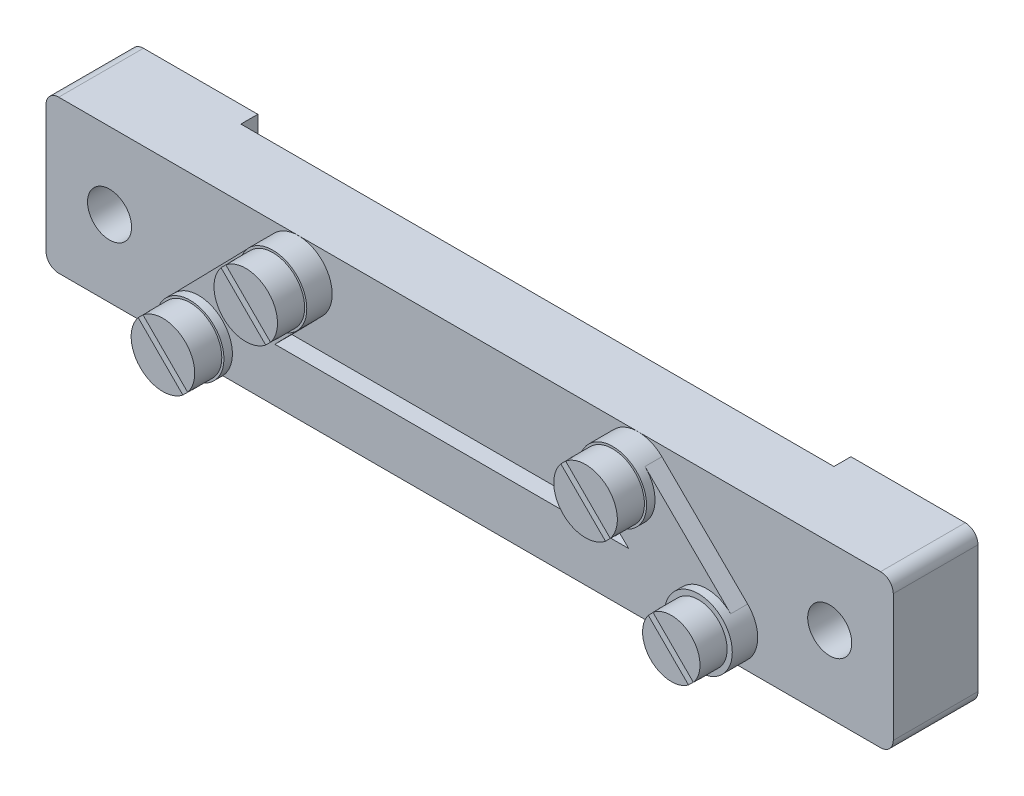
SolidWorks part; units mm, degrees
ref_plane "Спереди" through (0, 0, 0) normal (0, 0, 1) x (1, 0, 0)
ref_plane "Сверху" through (0, 0, 0) normal (0, 1, 0) x (1, 0, 0)
ref_plane "Справа" through (0, 0, 0) normal (1, 0, 0) x (0, 0, -1)
sketch "Эскиз1" plane through (0, 0, 0) normal (0, 0, 1) x (1, 0, 0)
  line L0 (0, 9) -> (100, 9) construction
  line L1 (0, 0) -> (100, 0)
  line L2 (0, 0) -> (0, 18)
  line L3 (0, 18) -> (100, 18)
  line L4 (100, 0) -> (100, 18)
  circle A0 centre (7.5, 9) radius 2.6
  circle A1 centre (92.5, 9) radius 2.6
  circle A2 centre (20, 4) radius 2
  circle A3 centre (80, 4) radius 2
  circle A4 centre (30, 14) radius 1.5
  circle A5 centre (70, 14) radius 1.5
  dimension "D3" = 85
  dimension "D4" = 7.5
  dimension "D5" = 5.2
  dimension "D6" = 60
  dimension "D7" = 20
  dimension "D8" = 40
  dimension "D9" = 30
  dimension "D10" = 4
  dimension "D11" = 4
  dimension "D12" = 4
  dimension "D13" = 4
  dimension "D14" = 3
  dimension "D15" = 4
  dimension "D1" = 100
  dimension "D2" = 18
extrude "Вытянуть1" add sketch "Эскиз1" along normal blind 10
sketch "Эскиз2" plane through (0, 0, 0) normal (0, 0, -1) x (-1, 0, 0)
  line L0 (0, 0) -> (-100, 0) construction
  line L1 (-85, 0) -> (-15, 0)
  line L2 (-85, 0) -> (-85, 18)
  line L3 (-85, 18) -> (-15, 18)
  line L4 (-15, 0) -> (-15, 18)
  line L5 (-100, 18) -> (0, 18) construction
  line L6 (-100, 0) -> (-100, 18) construction
  dimension "D1" = 70
  dimension "D2" = 15
extrude "Вырез-Вытянуть1" cut sketch "Эскиз2" against normal blind 2
fillet "Скругление1" radius 1.5
sketch "Эскиз3" plane through (0, 0, 10) normal (0, 0, 1) x (1, 0, 0)
  line L0 (72.6925, 16.8444) -> (82.8115, 6.8452)
  line L1 (29.0169, 7.5006) -> (70.7666, 7.5006)
  line L2 (22.8601, 1.2036) -> (77.1391, 1.2036)
  line L4 (77.1391, 1.2036) -> (77.1885, 1.1548)
  line L5 (67.0695, 11.1539) -> (70.7666, 7.5006)
  line L6 (32.6366, 11.2027) -> (29.0169, 7.5006)
  line L7 (26.9164, 16.7955) -> (17.1399, 6.7964)
  arc A2 (17.1399, 6.7964) -> (22.8601, 1.2036) centre (20, 4) ccw
  arc A3 (77.1885, 1.1548) -> (82.8115, 6.8452) centre (80, 4) ccw
  circle A4 centre (20, 4) radius 2 construction
  circle A5 centre (80, 4) radius 2 construction
  arc A6 (32.6366, 11.2027) -> (26.9164, 16.7955) centre (29.7765, 13.9991) ccw
  arc A7 (72.6925, 16.8444) -> (67.0695, 11.1539) centre (69.881, 13.9991) ccw
extrude "Вытянуть3" add sketch "Эскиз3" along normal blind 2
sketch "Эскиз4" plane through (0, 0, 12) normal (0, 0, 1) x (1, 0, 0)
  circle A0 centre (20, 4) radius 4
  circle A1 centre (29.7765, 13.9991) radius 4
  circle A2 centre (69.881, 13.9991) radius 4
  circle A3 centre (80, 4) radius 4
  arc A4 (17.1399, 6.7964) -> (22.8601, 1.2036) centre (20, 4) ccw construction
  arc A5 (32.6366, 11.2027) -> (26.9164, 16.7955) centre (29.7765, 13.9991) ccw construction
  arc A6 (77.1885, 1.1548) -> (82.8115, 6.8452) centre (80, 4) ccw construction
  arc A7 (72.6925, 16.8444) -> (67.0695, 11.1539) centre (69.881, 13.9991) ccw construction
  dimension "D1" = 8
  dimension "D2" = 8
  dimension "D3" = 8
extrude "Вытянуть4" add sketch "Эскиз4" along normal blind 1
sketch "Эскиз5" plane through (0, 0, 13) normal (0, 0, 1) x (1, 0, 0)
  circle A0 centre (80, 4) radius 3.3893
  circle A1 centre (80, 4) radius 4 construction
extrude "Вытянуть5" add sketch "Эскиз5" along normal blind 3.2
sketch "Эскиз6" plane through (0, 0, 13) normal (0, 0, 1) x (1, 0, 0)
  circle A0 centre (69.881, 13.9991) radius 3.75
  circle A1 centre (69.881, 13.9991) radius 4 construction
  dimension "D1" = 7.5
extrude "Вытянуть6" add sketch "Эскиз6" along normal blind 3.2
sketch "Эскиз7" plane through (0, 0, 13) normal (0, 0, 1) x (1, 0, 0)
  circle A0 centre (29.7765, 13.9991) radius 3.75
  circle A1 centre (29.7765, 13.9991) radius 4 construction
  dimension "D1" = 7.5
extrude "Вытянуть7" add sketch "Эскиз7" along normal blind 3.2
sketch "Эскиз8" plane through (0, 0, 13) normal (0, 0, 1) x (1, 0, 0)
  circle A0 centre (20, 4) radius 3.75
  circle A1 centre (20, 4) radius 4 construction
  dimension "D1" = 7.5
extrude "Вытянуть8" add sketch "Эскиз8" along normal blind 3.2
sketch "Эскиз9" plane through (0, 0, 16.2) normal (0, 0, 1) x (1, 0, 0)
  line L0 (16.1578, 7.2765) -> (24.0913, -0.657)
  line L1 (16.1578, 7.2765) -> (16.7235, 7.8422)
  line L2 (16.7235, 7.8422) -> (24.5967, -0.031)
  line L3 (24.5967, -0.031) -> (24.0913, -0.657)
  line L4 (1.5, 0) -> (20, 0) construction
  arc A1 (17.1399, 6.7964) -> (20, 0) centre (20, 4) ccw construction
  dimension "D1" = 45
  dimension "D2" = 0.4
  dimension "D3" = 0.8
extrude "Вырез-Вытянуть2" cut sketch "Эскиз9" against normal blind 1
sketch "Эскиз10" plane through (0, 0, 16.2) normal (0, 0, 1) x (1, 0, 0)
  line L0 (23.3324, 19.8776) -> (34.6539, 8.5561)
  line L1 (23.3324, 19.8776) -> (23.8981, 20.4433)
  line L2 (23.8981, 20.4433) -> (35.3336, 9.0077)
  line L3 (35.3336, 9.0077) -> (34.6539, 8.5561)
  line L4 (98.5, 18) -> (1.5, 18) construction
  circle A0 centre (29.7765, 13.9991) radius 4 construction
  dimension "D1" = 0.8
  dimension "D2" = 0.4
  dimension "D3" = 45
extrude "Вырез-Вытянуть3" cut sketch "Эскиз10" against normal blind 1
sketch "Эскиз11" plane through (0, 0, 16.2) normal (0, 0, 1) x (1, 0, 0)
  line L0 (62.8418, 20.4726) -> (84.7394, -1.4249)
  line L1 (63.5229, 20.923) -> (85.6958, -1.25)
  line L2 (85.6958, -1.25) -> (84.7394, -1.4249)
  line L3 (63.5229, 20.923) -> (62.8418, 20.4726)
  line L4 (98.5, 18) -> (1.5, 18) construction
  circle A0 centre (69.881, 13.9991) radius 4 construction
  dimension "D3" = 0.4
  dimension "D1" = 0.8
  dimension "D2" = 45
extrude "Вырез-Вытянуть4" cut sketch "Эскиз11" against normal blind 1
